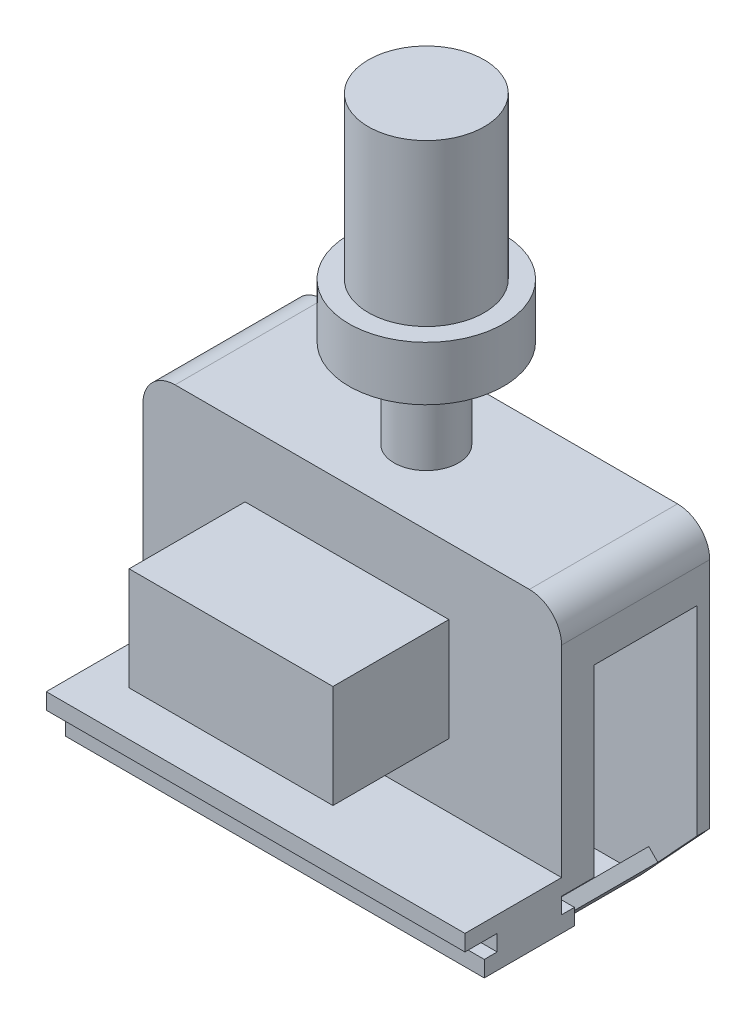
SolidWorks part; units mm, degrees
ref_plane "Front Plane" through (0, 0, 0) normal (0, 0, 1) x (1, 0, 0)
ref_plane "Top Plane" through (0, 0, 0) normal (0, 1, 0) x (1, 0, 0)
ref_plane "Right Plane" through (0, 0, 0) normal (1, 0, 0) x (0, 0, -1)
sketch "Sketch1" plane through (0, 0, 0) normal (0, 0, 1) x (1, 0, 0)
  line L0 (0, 0) -> (65, 0)
  line L1 (65, 0) -> (65, 2.5)
  line L2 (65, 2.5) -> (0, 2.5)
  line L3 (0, 2.5) -> (0, 0)
  line L4 (0, 2.5) -> (65, 2.5)
  line L5 (65, 5) -> (0, 5)
  line L6 (0, 5) -> (0, 2.5)
  line L7 (65, 2.5) -> (65, 5)
  line L8 (0, 7.5) -> (0, 5)
  line L9 (65, 7.5) -> (0, 7.5)
  line L10 (65, 5) -> (65, 7.5)
  line L11 (0, 5) -> (65, 5)
  line L12 (0, 7.5) -> (0, 38.75)
  line L13 (5, 43.75) -> (60, 43.75)
  line L14 (65, 38.75) -> (65, 7.5)
  line L16 (15.8591, 33.4474) -> (47.5056, 33.4474)
  line L17 (15.8591, 33.4474) -> (15.8591, 17.438)
  line L18 (15.8591, 17.438) -> (47.5056, 17.438)
  line L19 (47.5056, 33.4474) -> (47.5056, 17.438)
  arc A0 (5, 43.75) -> (0, 38.75) centre (5, 38.75) ccw
  arc A1 (60, 43.75) -> (65, 38.75) centre (60, 38.75) cw
  point P17 (0, 43.75)
  dimension "D5" = 5
  dimension "D1" = 2.5
  dimension "D2" = 65
  dimension "D3" = 65
  dimension "D4" = 36.25
extrude "Boss-Extrude1" add sketch "Sketch1" along normal blind 5 contours A1 L13 A0 L12 L9 L14 L16 L19 L18 L17 | L19 L16 L17 L18 region at (0.7442, 23.125, 0) region at (31.6824, 25.4427, 0)
extrude "Boss-Extrude2" add sketch "Sketch1<3>" along normal blind 20 contours L5 L10 L9 L8 region at (32.5, 6.25, 0)
sketch "Sketch1<3>" plane through (0, 0, 0) normal (0, 0, 1) x (1, 0, 0) same geometry as "Sketch1"
ref_plane "Plane1" through (0, 0, 10) normal (0, 0, 1) x (1, 0, 0)
sketch "Sketch2" plane through (0, 0, 10) normal (0, 0, 1) x (1, 0, 0)
  line L0 (65, 0) -> (65, 2.5) construction
  line L1 (0, 0) -> (65, 0) construction
  line L2 (0, 2.5) -> (0, 0) construction
  line L3 (0, 5) -> (0, 2.5) construction
  line L4 (65, 2.5) -> (65, 5) construction
  line L5 (65, 2.5) -> (0, 2.5) construction
  line L6 (65, 0) -> (65, 2.5)
  line L7 (0, 0) -> (65, 0)
  line L8 (0, 2.5) -> (0, 0)
  line L9 (0, 5) -> (0, 2.5)
  line L10 (65, 2.5) -> (65, 5)
  line L11 (65, 2.5) -> (0, 2.5)
  line L12 (65, 5) -> (0, 5) construction
  line L13 (65, 5) -> (0, 5)
extrude "Boss-Extrude3" add sketch "Sketch2" along normal mid plane 10 contours L10 L13 L9 L11 region at (32.5, 3.75, 10)
extrude "Boss-Extrude4" add sketch "Sketch2<3>" along normal mid plane 14 contours L6 L11 L8 L7 region at (32.5, 1.25, 10)
sketch "Sketch2<3>" plane through (0, 0, 10) normal (0, 0, 1) x (1, 0, 0) same geometry as "Sketch2"
extrude "Boss-Extrude5" add sketch "Sketch1<5>" along normal blind 23 contours L19 L16 L17 L18 region at (31.6824, 25.4427, 0)
sketch "Sketch1<5>" plane through (0, 0, 0) normal (0, 0, 1) x (1, 0, 0) same geometry as "Sketch1"
sketch "Sketch3" plane through (0, 0, 0) normal (0, 0, -1) x (-1, 0, 0)
  line L0 (0, 5) -> (0, 38.75) construction
  line L1 (-65, 38.75) -> (-65, 5) construction
  line L2 (-5, 43.75) -> (-60, 43.75) construction
  line L3 (0, 0.6947) -> (0, 38.75)
  line L4 (-65, 38.75) -> (-65, 2.5908)
  line L5 (-5, 43.75) -> (-60, 43.75)
  line L6 (-65, 2.5908) -> (-54.2902, -9.0096)
  line L8 (-54.2902, -9.0096) -> (-9.7042, -9.0096)
  line L9 (-9.7042, -9.0096) -> (0, 0.6947)
  line L10 (-63, 38.75) -> (-63, 3.3728)
  line L11 (-63, 3.3728) -> (-53.4146, -7.0096)
  line L12 (-53.4146, -7.0096) -> (-10.5327, -7.0096)
  line L13 (-10.5327, -7.0096) -> (-2, 1.5231)
  line L14 (-2, 1.5231) -> (-2, 38.75)
  line L15 (-5, 41.75) -> (-60, 41.75)
  line L16 (-63, 33.552) -> (-65, 33.552)
  line L17 (-57.5317, -2.5501) -> (-58.947, -3.9655)
  line L18 (-6.2663, -2.7432) -> (-4.8521, -4.1574)
  line L19 (-2, 33.674) -> (0, 33.674)
  arc A0 (0, 38.75) -> (-5, 43.75) centre (-5, 38.75) ccw construction
  arc A1 (-60, 43.75) -> (-65, 38.75) centre (-60, 38.75) ccw construction
  arc A2 (0, 38.75) -> (-5, 43.75) centre (-5, 38.75) ccw
  arc A3 (-60, 43.75) -> (-65, 38.75) centre (-60, 38.75) ccw
  arc A4 (-60, 41.75) -> (-63, 38.75) centre (-60, 38.75) ccw
  arc A5 (-2, 38.75) -> (-5, 41.75) centre (-5, 38.75) ccw
  point P30 (-65, 33.483)
  point P31 (-63, 33.552)
  arc M17 (-60, 43.75) -> (-65, 38.75) centre (-60, 38.75) ccw
  line M18 (-65, 38.75) -> (-65, 5)
  arc M21 (0, 38.75) -> (-5, 43.75) centre (-5, 38.75) ccw
  line M22 (-5, 43.75) -> (-60, 43.75)
  dimension "D1" = 2
extrude "Boss-Extrude6" add sketch "Sketch3" along normal blind 16 contours A5 L14 L19 L3 L16 L10 A4 L15 M21 M22 M17 M18 | L18 L13 L12 L11 L17 L6 L8 L9 region at (1, 34.332, 0) region at (31.9839, -7.4879, 0)
sketch "Sketch4" plane through (0, 0, -16) normal (0, 0, -1) x (-1, 0, 0)
  line L0 (-9.7042, -9.0096) -> (0, 0.6947) construction
  line L1 (-65, 2.5908) -> (-54.2902, -9.0096) construction
  line L2 (-65, 38.75) -> (-65, 2.5908) construction
  line L3 (0, 0.6947) -> (0, 38.75) construction
  line L4 (0, 33.674) -> (0, 38.75) construction
  line L5 (-9.7042, -9.0096) -> (-4.8521, -4.1574) construction
  line L6 (-54.2902, -9.0096) -> (-9.7042, -9.0096) construction
  line L7 (-58.947, -3.9655) -> (-54.2902, -9.0096) construction
  line L8 (-65, 38.75) -> (-65, 33.552) construction
  line L9 (-5, 43.75) -> (-60, 43.75) construction
  line L10 (-9.7042, -9.0096) -> (0, 0.6947)
  line L11 (-65, 2.5908) -> (-54.2902, -9.0096)
  line L12 (-65, 38.75) -> (-65, 2.5908)
  line L13 (0, 0.6947) -> (0, 38.75)
  line L14 (0, 33.674) -> (0, 38.75)
  line L15 (-9.7042, -9.0096) -> (-4.8521, -4.1574)
  line L16 (-54.2902, -9.0096) -> (-9.7042, -9.0096)
  line L17 (-58.947, -3.9655) -> (-54.2902, -9.0096)
  line L18 (-65, 38.75) -> (-65, 33.552)
  line L19 (-5, 43.75) -> (-60, 43.75)
  arc A0 (0, 38.75) -> (-5, 43.75) centre (-5, 38.75) ccw construction
  arc A1 (-60, 43.75) -> (-65, 38.75) centre (-60, 38.75) ccw construction
  arc A2 (0, 38.75) -> (-5, 43.75) centre (-5, 38.75) ccw
  arc A3 (-60, 43.75) -> (-65, 38.75) centre (-60, 38.75) ccw
  arc M1 (-5, 41.75) -> (-2, 38.75) centre (-5, 38.75) cw
  line M2 (-2, 38.75) -> (-2, 33.674)
  line M3 (-2, 33.674) -> (0, 33.674)
  line M4 (0, 33.674) -> (0, 38.75)
  arc M5 (0, 38.75) -> (-5, 43.75) centre (-5, 38.75) ccw
  line M6 (-5, 43.75) -> (-60, 43.75)
  arc M7 (-60, 43.75) -> (-65, 38.75) centre (-60, 38.75) ccw
  line M8 (-65, 38.75) -> (-65, 33.552)
  line M9 (-65, 33.552) -> (-63, 33.552)
  line M10 (-63, 33.552) -> (-63, 38.75)
  arc M11 (-63, 38.75) -> (-60, 41.75) centre (-60, 38.75) cw
  line M12 (-60, 41.75) -> (-5, 41.75)
extrude "Boss-Extrude7" add sketch "Sketch4" along normal blind 2 contours M12 M1 M2 M3 M4 M5 M6 M7 M8 M9 M10 M11 | L11 L16 L10 L13 L12 M3 M2 M1 M12 M11 M10 M9 region at (32.3647, 16.8744, -16) region at (1, 34.332, -16)
ref_plane "Plane2" through (0, 0, -6.5) normal (0, 0, 1) x (1, 0, 0)
sketch "Sketch5" plane through (0, 0, -6.5) normal (0, 0, 1) x (1, 0, 0)
  line L0 (32.5, 92.4082) -> (32.5, 30.9192) construction
  line L1 (65, 38.75) -> (65, 7.5) construction
  line L2 (0, 7.5) -> (0, 38.75) construction
  line L3 (65, 38.75) -> (65, 7.5)
  line L4 (0, 7.5) -> (0, 38.75)
  line L5 (5, 43.75) -> (60, 43.75) construction
  line L6 (5, 43.75) -> (60, 43.75)
  line L7 (27.5, 57.55) -> (38.5122, 57.55)
  line L8 (27.5, 57.55) -> (27.5, 43.75)
  line L9 (38.2766, 65.95) -> (20.5, 65.95)
  line L10 (20.5, 65.95) -> (20.5, 57.55)
  line L11 (20.5, 57.55) -> (27.5, 57.55)
  line L12 (23.5, 65.95) -> (23.5, 90.95)
  line L13 (23.5, 90.95) -> (33.2359, 90.95)
  point P13 (32.5, 96.8262)
  point P18 (32.5, 40.0571)
  point P19 (32.5, 95.8046)
  point P20 (32.5, 46.6624)
  point P21 (32.5, 30.9192)
  dimension "D1" = 32.5
  dimension "D2" = 65
  dimension "D3" = 13.8
  dimension "D4" = 8.4
  dimension "D6" = 12
  dimension "D7" = 5
  dimension "D8" = 9
  dimension "D9" = 25
revolve "Revolve1" add sketch "Sketch5" angle 360 about L0 region at (28, 78.45, -6.5) region at (26.5, 61.75, -6.5) region at (30, 50.65, -6.5)
